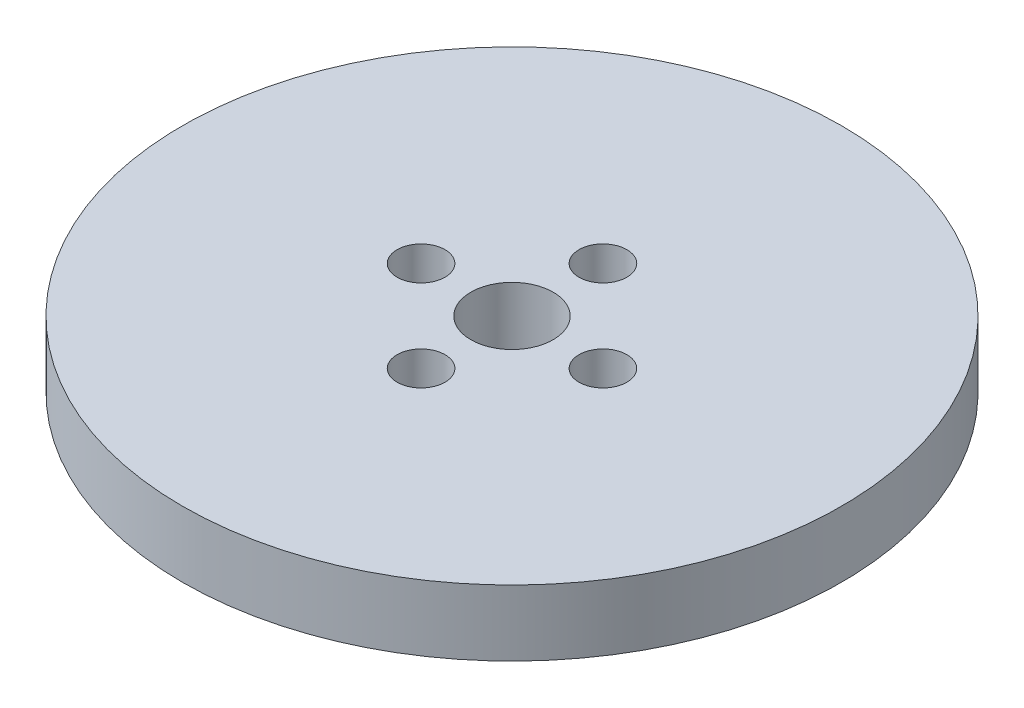
SolidWorks part; units mm, degrees
ref_plane "Front Plane" through (0, 0, 0) normal (0, 0, 1) x (1, 0, 0)
ref_plane "Top Plane" through (0, 0, 0) normal (0, 1, 0) x (1, 0, 0)
ref_plane "Right Plane" through (0, 0, 0) normal (1, 0, 0) x (0, 0, -1)
sketch "Sketch1" plane through (0, 0, 0) normal (0, 1, 0) x (1, 0, 0)
  circle A0 centre (0, 0) radius 40
  dimension "FLANGE_OD" = 80
extrude "Boss-Extrude1" add sketch "Sketch1" along normal blind 8
sketch "Sketch2" plane through (0, 0, 0) normal (0, 1, 0) x (1, 0, 0)
  circle A0 centre (0, 0) radius 5
  dimension "BORE_D" = 10
extrude "Cut-Extrude1" cut sketch "Sketch2" along normal through all
sketch "Sketch3" plane through (0, 8, 0) normal (0, 1, 0) x (1, 0, 0)
  circle A0 centre (0, 0) radius 11.0373 construction
  circle A1 centre (-11.0373, 0) radius 2.905
  dimension "BOLT_D" = 5.81
  dimension "BOLT_PCD" = 22.0746
extrude "Cut-Extrude2" cut sketch "Sketch3" against normal blind 6.5603
pattern_circular "CirPattern1" count 4 over 360 about axis through (0, 0, 0) along (0, 1, 0) of "Cut-Extrude2"
